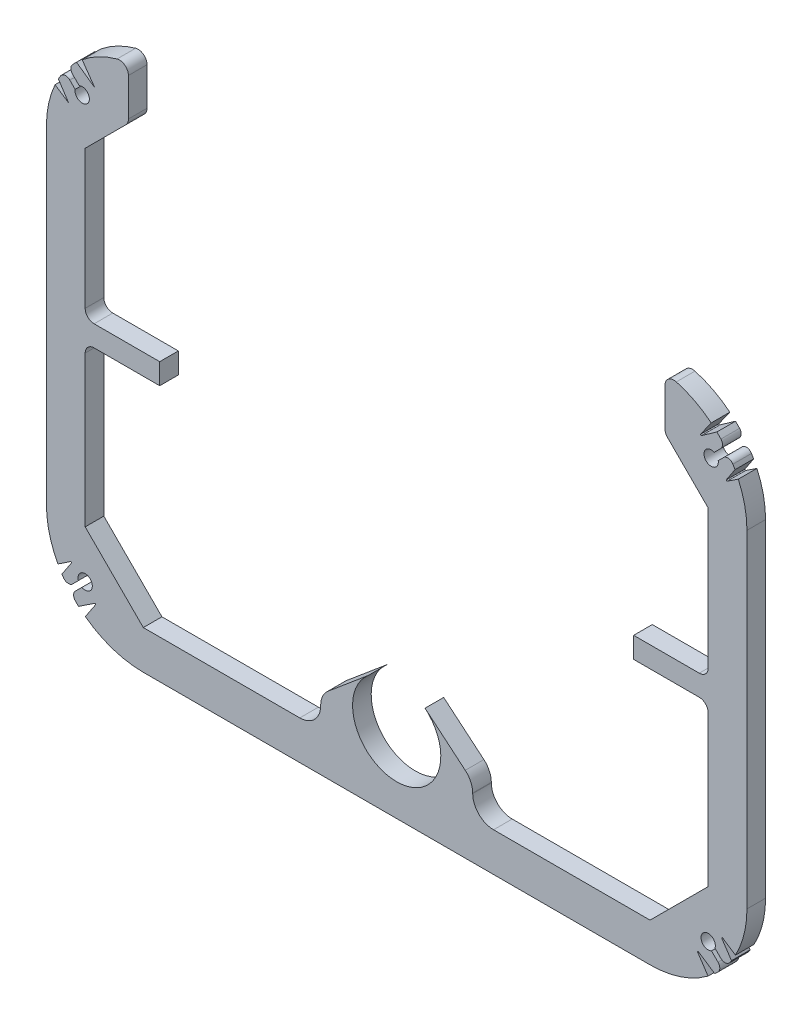
SolidWorks part; units mm, degrees
material "Delrin 2700 NC010, Low Viscosity Acetal Copolymer (SS)"
ref_plane "Front Plane" through (0, 0, 0) normal (0, 0, 1) x (1, 0, 0)
ref_plane "Top Plane" through (0, 0, 0) normal (0, 1, 0) x (1, 0, 0)
ref_plane "Right Plane" through (0, 0, 0) normal (1, 0, 0) x (0, 0, -1)
sketch "Sketch1" plane through (0, 0, 0) normal (0, 0, 1) x (1, 0, 0)
  line L0 (-21.59, -18.923) -> (-9.6321, -18.923)
  line L1 (21.59, 22.225) -> (-21.59, 22.225)
  line L2 (29.845, 13.97) -> (29.845, -13.97)
  line L3 (21.59, -22.225) -> (-21.59, -22.225)
  line L4 (-29.845, 13.97) -> (-29.845, -13.97)
  line L5 (29.845, 22.225) -> (-29.845, -22.225) construction
  line L6 (29.845, -22.225) -> (-29.845, 22.225) construction
  line L7 (9.6321, -18.923) -> (21.59, -18.923)
  line L8 (-26.543, -0.381) -> (-20.193, -0.381)
  line L9 (26.543, 1.397) -> (20.193, 1.397)
  line L10 (-26.543, 13.97) -> (-26.543, -13.97)
  line L11 (-1000, 0) -> (49000, 0) construction
  line L12 (-26.543, 0) -> (-26.543, -1.27)
  line L13 (26.543, 13.97) -> (26.543, -13.97)
  line L14 (21.59, 18.923) -> (-21.59, 18.923)
  line L15 (26.543, 1.397) -> (26.543, -0.381)
  line L16 (26.543, -0.381) -> (20.193, -0.381)
  line L17 (20.193, 1.397) -> (20.193, -0.381)
  line L18 (0, 18.923) -> (0, -18.415) construction
  line L19 (-20.193, 1.397) -> (-20.193, -0.381)
  line L20 (-26.543, 1.397) -> (-20.193, 1.397)
  line L21 (2.4164, -12.8683) -> (9.6321, -18.923)
  line L22 (-2.4164, -12.8683) -> (-9.6321, -18.923)
  line L23 (26.543, 13.97) -> (21.59, 18.923)
  line L24 (-21.59, 18.923) -> (-26.543, 13.97)
  line L25 (26.543, -13.97) -> (21.59, -18.923)
  line L27 (-26.543, -13.97) -> (-21.59, -18.923)
  line L36 (21.59, -18.923) -> (-21.59, -18.923) construction
  arc A0 (-2.4164, -12.8683) -> (2.4164, -12.8683) centre (0, -15.748) ccw
  arc A1 (-21.59, 22.225) -> (-29.845, 13.97) centre (-21.59, 13.97) ccw
  arc A2 (21.59, 22.225) -> (29.845, 13.97) centre (21.59, 13.97) cw
  arc A3 (29.845, -13.97) -> (21.59, -22.225) centre (21.59, -13.97) cw
  arc A4 (-21.59, -22.225) -> (-29.845, -13.97) centre (-21.59, -13.97) cw
  arc A13 (-21.59, -18.923) -> (-26.543, -13.97) centre (-21.59, -13.97) cw construction
  arc A14 (26.543, -13.97) -> (21.59, -18.923) centre (21.59, -13.97) cw construction
  arc A17 (21.59, 18.923) -> (26.543, 13.97) centre (21.59, 13.97) cw construction
  arc A18 (-21.59, 18.923) -> (-26.543, 13.97) centre (-21.59, 13.97) ccw construction
  point P0 (0, 0)
  dimension "D4" = 7.5184
  dimension "D6" = 8.255
  dimension "D7" = 8.255
  dimension "D8" = 8.255
  dimension "D9" = 8.255
  dimension "D1" = 59.69
  dimension "D2" = 44.45
  dimension "D10" = 3.302
  dimension "D3" = 3.175
  dimension "D13" = 15.748
  dimension "D14" = 1.778
  dimension "D15" = 21.844
  dimension "D16" = 6.35
extrude "Boss-Extrude1" add sketch "Sketch1" along normal blind 1.5875 contours A4 L3 A3 L2 A2 L1 A1 L4 L25 L7 L21 A0 L22 L0 L27 L10 L24 L14 L23 L13 | L9 L17 L16 L13 | L20 L10 L8 L19 region at (-23.368, 0.508, 0) region at (23.368, 0.508, 0) region at (26.9009, 19.2809, 0)
sketch "Sketch2" plane through (0, 0, 1.5875) normal (0, 0, 1) x (1, 0, 0)
  line L1 (-9.6321, -18.923) -> (-6.477, -18.923)
  line L2 (-9.6321, -18.923) -> (-9.6321, -16.2756)
  line L3 (-9.6321, -16.2756) -> (-6.477, -16.2756)
  line L4 (-6.477, -18.923) -> (-6.477, -16.2756)
  line L5 (0, -1000) -> (0, 49000) construction
  line L6 (9.6321, -18.923) -> (9.6321, -16.2756)
  line L7 (9.6321, -16.2756) -> (6.477, -16.2756)
  line L8 (6.477, -18.923) -> (6.477, -16.2756)
  line L9 (9.6321, -18.923) -> (6.477, -18.923)
  line L10 (-29.845, 13.97) -> (-29.845, -13.97) construction
  line L11 (-21.59, 18.923) -> (21.59, 18.923)
  line L12 (-22.86, 17.653) -> (-22.86, 22.225)
  line L13 (-22.86, 22.225) -> (22.86, 22.225)
  line L14 (22.86, 17.653) -> (22.86, 22.225)
  line L15 (26.543, 13.97) -> (21.59, 18.923) construction
  line L16 (21.59, 18.923) -> (-21.59, 18.923) construction
  line L17 (-2.4164, -12.8683) -> (-9.6321, -18.923) construction
  line L18 (21.59, 22.225) -> (-21.59, 22.225) construction
  line L19 (22.86, 17.653) -> (21.59, 18.923)
  line L20 (-21.59, 18.923) -> (-26.543, 13.97) construction
  line L21 (-21.59, 18.923) -> (-22.86, 17.653)
  point P25 (0, 22.225)
  dimension "D1" = 6.477
  dimension "D2" = 6.985
extrude "Cut-Extrude1" cut sketch "Sketch2" against normal up to next
fillet "Fillet1" radius 1.778 4 edges at (6.477, -18.923, 0.7937) (6.477, -16.2756, 0.7937) (-6.477, -18.923, 0.7937) (-6.477, -16.2756, 0.7937)
fillet "Fillet2" radius 0.762 4 edges at (22.86, 22.1267, 0.7937) (22.86, 17.653, 0.7937) (-22.86, 17.653, 0.7937) (-22.86, 22.1267, 0.7937)
fillet "Fillet3" radius 0.762 4 edges at (-26.543, -0.381, 0.7937) (26.543, -0.381, 0.7937) (26.543, 1.397, 0.7937) (-26.543, 1.397, 0.7937)
sketch "Sketch3" plane through (0, 0, 1.5875) normal (0, 0, 1) x (1, 0, 0)
  circle A0 centre (-25.019, -16.51) radius 0.6096 construction
  circle A1 centre (-25.019, 16.256) radius 0.6096 construction
  circle A2 centre (25.019, 16.256) radius 0.6096 construction
  circle A3 centre (25.019, -16.51) radius 0.6096 construction
  circle A4 centre (-25.019, -16.51) radius 0.6096 construction
  circle A5 centre (-25.019, 16.256) radius 0.6096 construction
  circle A6 centre (25.019, 16.256) radius 0.6096 construction
  circle A7 centre (25.019, -16.51) radius 0.6096 construction
  circle A8 centre (-26.797, 17.78) radius 0.6096
  circle A9 centre (-26.543, -18.034) radius 0.6096
  circle A10 centre (26.797, 17.78) radius 0.6096
  circle A11 centre (26.543, -18.034) radius 0.6096
  dimension "D1" = 1.524
  dimension "D2" = 1.778
  dimension "D3" = 1.524
  dimension "D4" = 1.524
  dimension "D5" = 1.778
  dimension "D6" = 1.524
extrude "Cut-Extrude2" cut sketch "Sketch3" against normal up to surface (1.5875 mm away) up to face at (0, -2.166, 0)
sketch "Sketch4" plane through (0, 0, 0) normal (0, 0, -1) x (-1, 0, 0)
  line L0 (-27.0554, 18.3321) -> (-27.9527, 19.2294)
  line L1 (-29.845, 13.97) -> (-29.845, -13.97) construction
  line L2 (-28.2939, 18.7869) -> (-27.3967, 17.8896)
  circle A1 centre (-26.797, 17.78) radius 0.6096 construction
  arc A2 (-23.8286, 21.9157) -> (-29.845, 13.97) centre (-21.59, 13.97) ccw construction
  arc A3 (-27.9527, 19.2294) -> (-28.2939, 18.7869) centre (-21.59, 13.97) ccw
  arc A4 (-27.0554, 18.3321) -> (-27.3967, 17.8896) centre (-26.797, 17.78) ccw
  point P11 (0, 0)
  dimension "D1" = 0.5588
  dimension "D2" = 135
extrude "Cut-Extrude3" cut sketch "Sketch4" against normal up to surface (1.5875 mm away) up to face at (27.1526, -18.034, 1.5875)
sketch "Sketch5" plane through (0, 0, 0) normal (0, 0, -1) x (-1, 0, 0)
  line L0 (-27.1221, -18.2245) -> (-28.0309, -19.1333)
  line L1 (-8.255, -18.923) -> (-21.59, -18.923) construction
  line L2 (-27.7341, -19.4831) -> (-26.8253, -18.5743)
  circle A0 centre (-26.543, -18.034) radius 0.6096 construction
  arc A1 (-29.845, -13.97) -> (-21.59, -22.225) centre (-21.59, -13.97) ccw construction
  arc A2 (-28.0309, -19.1333) -> (-27.7341, -19.4831) centre (-21.59, -13.97) ccw
  arc A3 (-27.1221, -18.2245) -> (-26.8253, -18.5743) centre (-26.543, -18.034) ccw
  dimension "D2" = 0.4572
  dimension "D1" = 45
extrude "Cut-Extrude4" cut sketch "Sketch5" against normal through all
sketch "Sketch9" plane through (0, 0, 0) normal (0, 0, -1) x (-1, 0, 0)
  line L0 (-28.6475, -18.6235) -> (-28.917, -18.3541)
  line L1 (-29.1864, -18.0847) -> (-27.5699, -17.0071)
  line L2 (-26.543, -18.034) -> (-26.2345, -18.3425) construction
  line L3 (-28.6475, -18.6235) -> (-27.5699, -17.0071)
  line L4 (-36.9627, -28.4537) -> (-27.128, -18.619) construction
  line L5 (-27.5699, -17.0071) -> (-33.3479, -22.7851) construction
  line L6 (-28.917, -18.3541) -> (-29.1864, -18.0847)
  line L7 (-26.2345, -18.3425) -> (-25.5161, -19.0609) construction
  line L8 (-25.5161, -19.0609) -> (-32.2288, -25.7736) construction
  line L9 (-26.8631, -20.408) -> (-27.1325, -20.1385)
  line L10 (-27.1325, -20.1385) -> (-25.5161, -19.0609)
  line L11 (-25.5161, -19.0609) -> (-26.5937, -20.6774)
  line L12 (-26.543, -18.034) -> (-26.8515, -17.7255) construction
  line L13 (-26.8515, -17.7255) -> (-27.5699, -17.0071) construction
  line L14 (-26.5937, -20.6774) -> (-26.8631, -20.408)
  arc A0 (-26.8253, -18.5743) -> (-27.1221, -18.2245) centre (-26.543, -18.034) ccw construction
  dimension "D1" = 0.762
  dimension "D2" = 1.016
  dimension "D3" = 1.016
  dimension "D4" = 0.762
  dimension "D5" = 1.905
  dimension "D6" = 1.905
extrude "Cut-Extrude6" cut sketch "Sketch9" against normal through all
mirror "Mirror3" about plane through (0, 0, 0) normal (1, 0, 0) of "Cut-Extrude6", "Cut-Extrude4"
sketch "Sketch7" plane through (0, 0, 0) normal (0, 0, -1) x (-1, 0, 0)
  line L0 (-27.5514, 20.1365) -> (-27.282, 20.4059)
  line L1 (-27.0126, 20.6753) -> (-25.7265, 18.8505)
  line L2 (-26.797, 17.78) -> (-27.2394, 17.3376) construction
  line L3 (-27.5514, 20.1365) -> (-25.7265, 18.8505)
  line L4 (-25.9064, 16.7912) -> (-19.983, 10.8678) construction
  line L5 (-25.7265, 18.8505) -> (-29.3063, 22.4302) construction
  line L6 (-27.282, 20.4059) -> (-27.0126, 20.6753)
  line L7 (-27.2394, 17.3376) -> (-27.9579, 16.6191) construction
  line L8 (-27.9579, 16.6191) -> (-32.2296, 20.8909) construction
  line L9 (-29.2706, 17.9319) -> (-29.0012, 18.2013)
  line L10 (-29.0012, 18.2013) -> (-27.9579, 16.6191)
  line L11 (-27.9579, 16.6191) -> (-29.54, 17.6625)
  line L12 (-26.797, 17.78) -> (-26.445, 18.132) construction
  line L13 (-26.445, 18.132) -> (-25.7265, 18.8505) construction
  line L14 (-29.54, 17.6625) -> (-29.2706, 17.9319)
  line L15 (-27.0554, 18.3321) -> (-27.9527, 19.2294) construction
  line L16 (-28.2939, 18.7869) -> (-27.3967, 17.8896) construction
  arc A0 (-27.3967, 17.8896) -> (-27.0554, 18.3321) centre (-26.797, 17.78) ccw construction
  dimension "D1" = 0.762
  dimension "D2" = 1.016
  dimension "D3" = 1.016
  dimension "D4" = 0.762
extrude "Cut-Extrude5" cut sketch "Sketch7" against normal through all
fillet "Fillet5" radius 0.0508 6 edges at (25.7265, 18.8505, 0.7938) (27.9579, 16.6191, 0.7938) (-27.5699, -17.0071, 0.7938) (-25.5161, -19.0609, 0.7938) (25.5161, -19.0609, 0.7938) (27.5699, -17.0071, 0.7938)
mirror "Mirror1" about plane through (0, 0, 0) normal (1, 0, 0) of "Cut-Extrude3", "Cut-Extrude5"
fillet "Fillet4" radius 0.508 8 edges at (27.9527, 19.2294, 0.7938) (28.2939, 18.7869, 0.7937) (-28.2939, 18.7869, 0.7938) (-27.9527, 19.2294, 0.7938) (-27.7341, -19.4831, 0.7938) (-28.0309, -19.1333, 0.7938) (27.7341, -19.4831, 0.7938) (28.0309, -19.1333, 0.7938)
equation "\"SnapInRodSlotSize\"=0.02"
